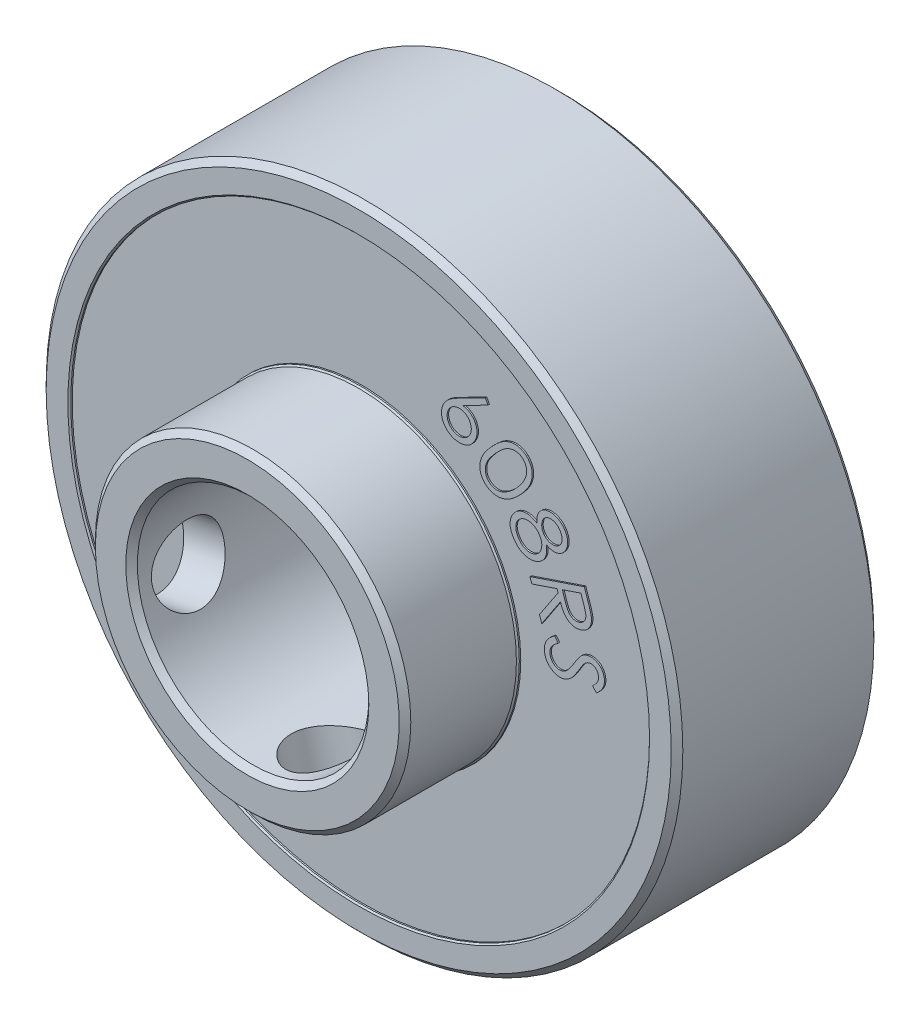
SolidWorks part; units mm, degrees
material "AISI 1020"
ref_plane "Front Plane" through (0, 0, 0) normal (0, 0, 1) x (1, 0, 0)
ref_plane "Top Plane" through (0, 0, 0) normal (0, 1, 0) x (1, 0, 0)
ref_plane "Right Plane" through (0, 0, 0) normal (1, 0, 0) x (0, 0, -1)
sketch "Sketch1" plane through (0, 0, 0) normal (0, 0, 1) x (1, 0, 0)
  circle A0 centre (0, 0) radius 11
  circle A1 centre (0, 0) radius 4
extrude "Boss-Extrude1" add sketch "Sketch1" along normal blind 7
sketch "Sketch2" plane through (0, 0, 7) normal (0, 0, 1) x (1, 0, 0)
  circle A0 centre (0, 0) radius 5.5
  circle A1 centre (0, 0) radius 10
extrude "Cut-Extrude1" cut sketch "Sketch2" against normal blind 0.1
extrude "Cut-Extrude2" cut sketch "Sketch2<2>" against normal blind 0.1 from offset 6.9 offset against normal yes
sketch "Sketch2<2>" plane through (0, 0, 7) normal (0, 0, 1) x (1, 0, 0) same geometry as "Sketch2"
chamfer "Chamfer2" distance 0.05 angle 45 4 edges at (5.5, 0, 7) (10, 0, 7) (10, 0, 0) (5.5, 0, 0)
sketch "Esboço2" plane through (0, 0, 7) normal (0, 0, 1) x (1, 0, 0)
  circle A0 centre (0, 0) radius 5.45
  circle A1 centre (0, 0) radius 4
extrude "Ressalto-extrusão1" add sketch "Esboço2" along normal blind 3.85
sketch "Sketch3" plane through (0, 0, 0.1) normal (0, 0, -1) x (-1, 0, 0)
  circle A0 centre (0, 0) radius 6.5 construction
  text T0 "608RS" font "Century Gothic" height 2
extrude "Boss-Extrude2" add sketch "Sketch3" along normal blind 0.05
chamfer "Chamfer1" distance 0.2 angle 45 5 edges at (4, 0, 0) (11, 0, 7) (11, 0, 0) (5.45, 0, 10.85) (4, 0, 10.85)
sketch "Sketch4" plane through (0, 0, 6.9) normal (0, 0, 1) x (1, 0, 0)
  circle A0 centre (0, 0) radius 6.5 construction
  text T0 "608RS" font "Century Gothic" height 2
extrude "Boss-Extrude3" add sketch "Sketch4" along normal blind 0.05
hole_wizard "Furo roscado de M31" positions "3DSketch1" profile "Esboço3" tap size "M3" standard "ISO"
sketch3d "3DSketch1"
  point P0 (-5.3555, -1.0105, 8.9668)
  point P2 (1.3573, -5.2783, 9.0638)
sketch "Esboço3" plane through (-5.3555, -1.0105, 8.9668) normal (0, 0, 1) x (0.1854, -0.9827, 0)
  line L0 (0, 0) -> (0, 8.2511)
  line L1 (0, 8.2511) -> (1.25, 7.5)
  line L2 (1.25, 7.5) -> (1.25, 0)
  line L5 (1.25, 0) -> (0, 0)
  line L10 (0, 8.2511) -> (-1.25, 7.5) construction
  line L11 (0, -6.35) -> (0, 107.95) construction
  dimension "Tap Drill Dia." = 2.5
  dimension "Tap Drill Depth" = 7.5
  dimension "Drill Angle" = 118
sketch "Sketch5" plane through (0, 0, 0) normal (1, 0, 0) x (0, 0, -1)
  line L0 (0, -10.8) -> (0, 10.8) construction
  circle A0 centre (-3.5, 0) radius 1
  dimension "D1" = 3.5
scale "Scale1" scale about origin uniform scaling yes scale factor 1.25
